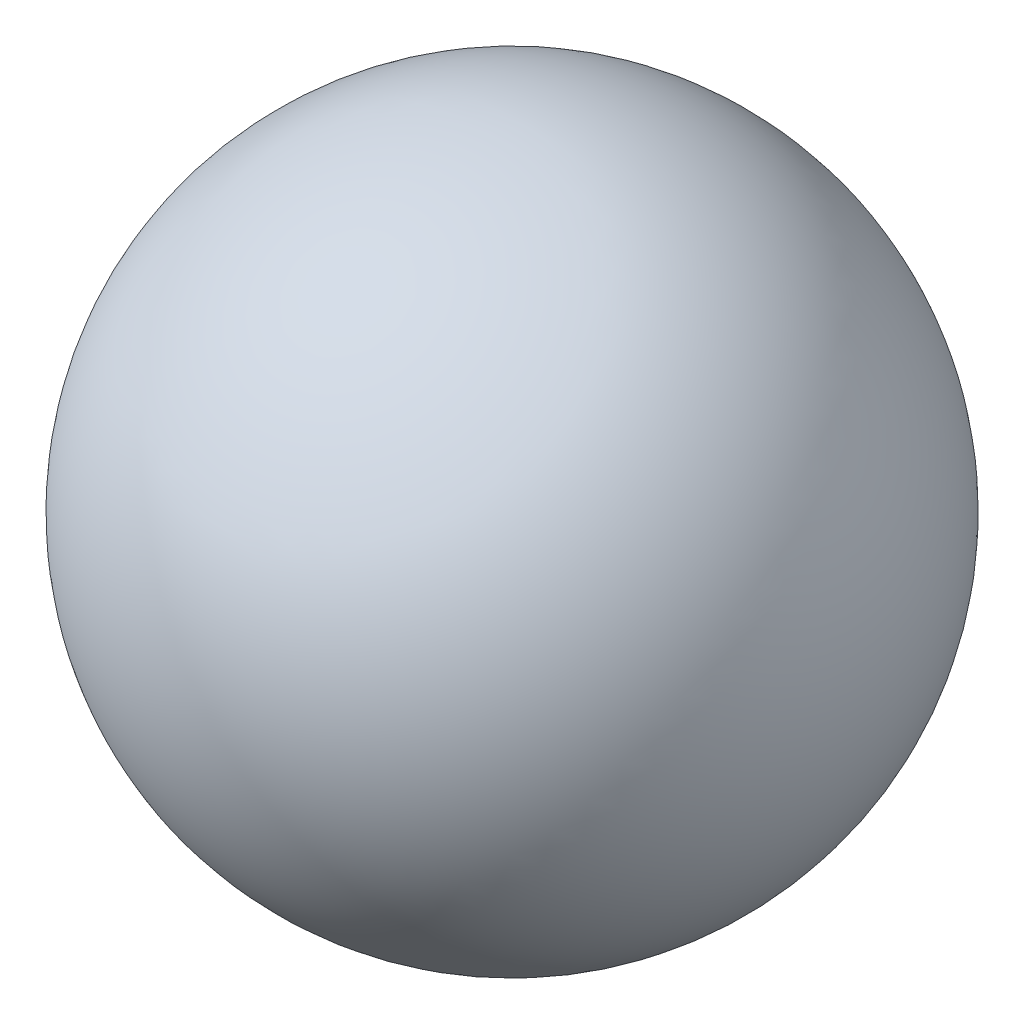
SolidWorks part; units mm, degrees
ref_plane "Front Plane" through (0, 0, 0) normal (0, 0, 1) x (1, 0, 0)
ref_plane "Top Plane" through (0, 0, 0) normal (0, 1, 0) x (1, 0, 0)
ref_plane "Right Plane" through (0, 0, 0) normal (1, 0, 0) x (0, 0, -1)
sketch "Sketch1" plane through (0, 0, 0) normal (0, 1, 0) x (1, 0, 0)
  line L0 (0, -7.6073) -> (0, 7.6073)
  circle A0 centre (0, 0) radius 7.6073
  dimension "D1" = 15.2146
revolve "Revolve2" add sketch "Sketch1" angle 360 about L0 region at (-3.2286, 0, 0)
